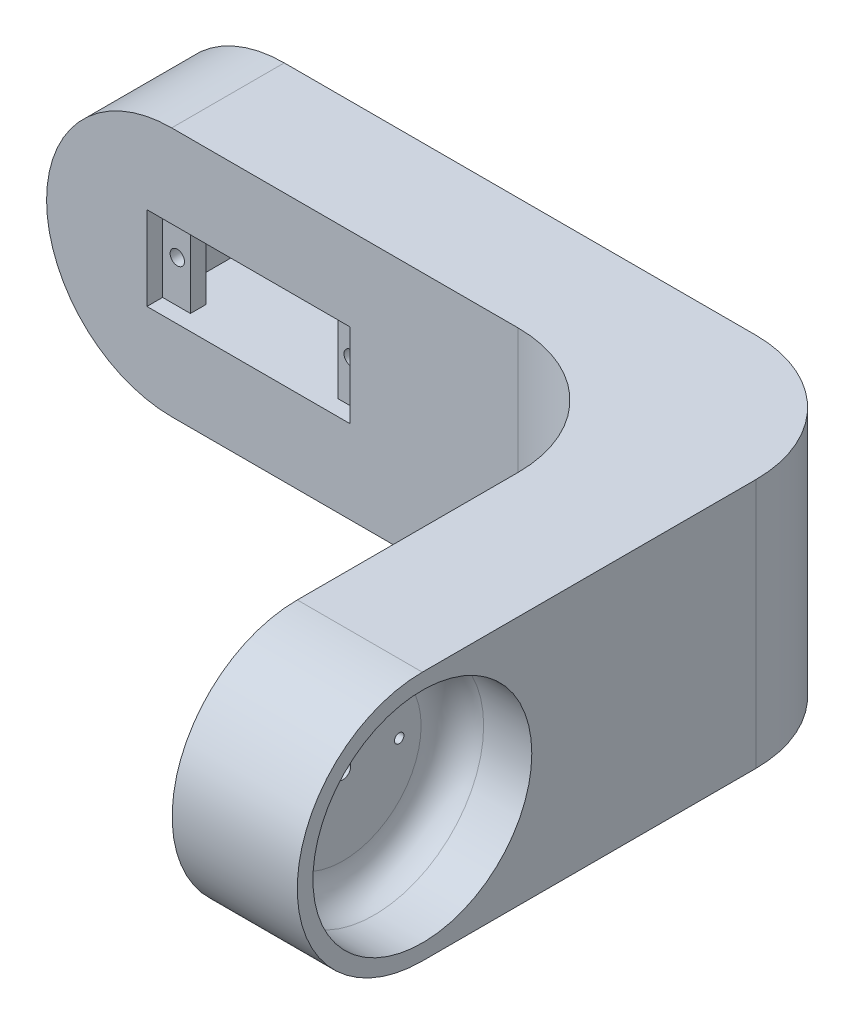
SolidWorks part; units mm, degrees
ref_plane "Front Plane" through (0, 0, 0) normal (0, 0, 1) x (1, 0, 0)
ref_plane "Top Plane" through (0, 0, 0) normal (0, 1, 0) x (1, 0, 0)
ref_plane "Right Plane" through (0, 0, 0) normal (1, 0, 0) x (0, 0, -1)
sketch "Sketch1" plane through (0, 0, 0) normal (1, 0, 0) x (0, 0, -1)
  line L1 (0, 20) -> (73.32, 20)
  line L2 (0, 20) -> (0, -20)
  line L3 (0, -20) -> (73.32, -20)
  line L4 (73.32, 20) -> (73.32, -20)
  circle A0 centre (0, 0) radius 20
  dimension "D1" = 40
  dimension "D2" = 73.32
extrude "Boss-Extrude1" add sketch "Sketch1" along normal blind 20 contours A0 L3 L4 L1 | L2 A0 | L2 A0 region at (0, 0, -8.4883) region at (0, 0, -44.341) region at (0, 0, 8.4883)
sketch "Sketch2" plane through (20, 0, 0) normal (1, 0, 0) x (0, 0, -1)
  circle A0 centre (0, 0) radius 17.5
  dimension "D1" = 35
extrude "Cut-Extrude1" cut sketch "Sketch2" against normal blind 12.7
sketch "Sketch3" plane through (0, 0, 0) normal (-1, 0, 0) x (0, 0, 1)
  circle A0 centre (0, 0) radius 17.5
  dimension "D1" = 35
extrude "Cut-Extrude2" cut sketch "Sketch3" against normal blind 4.8
sketch "Sketch4" plane through (4.8, 0, 0) normal (-1, 0, 0) x (0, 0, 1)
  circle A0 centre (0, 0) radius 1.25
  circle A1 centre (-9, 0) radius 0.75
  circle A2 centre (9, 0) radius 0.75
  dimension "D1" = 2.5
  dimension "D2" = 9
  dimension "D3" = 9
  dimension "D4" = 1.5
  dimension "D5" = 1.5
extrude "Cut-Extrude3" cut sketch "Sketch4" against normal blind 4.8
sketch "Sketch5" plane through (0, 0, 0) normal (-1, 0, 0) x (0, 0, 1)
  line L0 (0, -20) -> (-73.32, -20) construction
  line L1 (-73.32, 20) -> (-55.32, 20)
  line L2 (-73.32, 20) -> (-73.32, -20)
  line L3 (-73.32, -20) -> (-55.32, -20)
  line L4 (-55.32, 20) -> (-55.32, -20)
  dimension "D1" = 18
extrude "Boss-Extrude2" add sketch "Sketch5" along normal blind 95.4
fillet "Fillet1" radius 20 2 edges at (-95.4, -20, -64.32) (-95.4, 20, -64.32)
sketch "Sketch7" plane through (0, 0, -55.32) normal (0, 0, 1) x (1, 0, 0)
  line L0 (20, -20) -> (20, 20) construction
  line L1 (-79.35, 6.7) -> (-46.85, 6.7)
  line L2 (-79.35, 6.7) -> (-79.35, -6.7)
  line L3 (-79.35, -6.7) -> (-46.85, -6.7)
  line L4 (-46.85, 6.7) -> (-46.85, -6.7)
  line L5 (-75.4, 20) -> (0, 20) construction
  dimension "D1" = 32.5
  dimension "D2" = 13.4
  dimension "D3" = 66.85
  dimension "D4" = 13.3
extrude "Cut-Extrude4" cut sketch "Sketch7" against normal blind 2.5
fillet "Fillet2" radius 5 2 edges at (4.8, 0, 17.5) (7.3, 0, -17.5)
fillet "Fillet3" radius 20 2 edges at (20, 0, -73.32) (0, 0, -55.32)
sketch "Sketch8" plane through (0, 0, -73.32) normal (0, 0, -1) x (-1, 0, 0)
  line L0 (0, 20) -> (75.4, 20) construction
  line L1 (46.85, 6.7) -> (79.35, 6.7)
  line L2 (46.85, 6.7) -> (46.85, -6.7)
  line L3 (46.85, -6.7) -> (79.35, -6.7)
  line L4 (79.35, 6.7) -> (79.35, -6.7)
  line L5 (-20, -20) -> (-20, 20) construction
  dimension "D1" = 32.5
  dimension "D2" = 13.4
  dimension "D3" = 13.3
  dimension "D4" = 66.85
extrude "Cut-Extrude5" cut sketch "Sketch8" against normal blind 13
sketch "Sketch9" plane through (0, 0, -57.82) normal (0, 0, 1) x (1, 0, 0)
  line L0 (-46.85, 6.7) -> (-79.35, 6.7) construction
  line L1 (-74.9, 6.7) -> (-51.3, 6.7)
  line L2 (-74.9, 6.7) -> (-74.9, -6.7)
  line L3 (-74.9, -6.7) -> (-51.3, -6.7)
  line L4 (-51.3, 6.7) -> (-51.3, -6.7)
  line L5 (-79.35, -6.7) -> (-46.85, -6.7) construction
  line L6 (-79.35, 6.7) -> (-79.35, -6.7) construction
  circle A0 centre (-77, 0) radius 1.15
  circle A1 centre (-49.2, 0) radius 1.15
  dimension "D3" = 2.3
  dimension "D4" = 2.3
  dimension "D5" = 2.1
  dimension "D6" = 2.1
  dimension "D1" = 23.6
  dimension "D2" = 4.45
extrude "Cut-Extrude6" cut sketch "Sketch9" against normal blind 13
